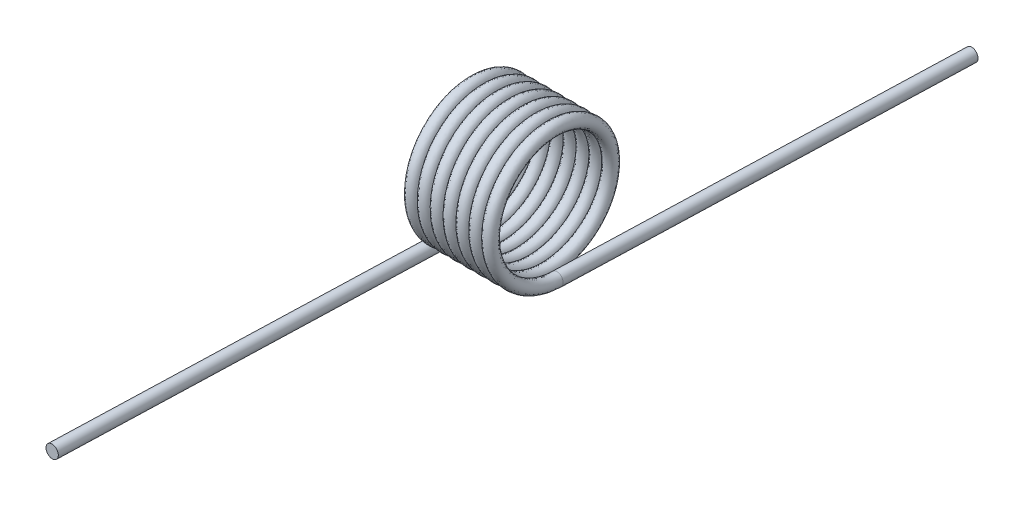
SolidWorks part; units mm, degrees
material "music wire"
ref_plane "Front" through (0, 0, 0) normal (0, 0, 1) x (1, 0, 0)
ref_plane "Top" through (0, 0, 0) normal (0, 1, 0) x (1, 0, 0)
ref_plane "Right" through (0, 0, 0) normal (1, 0, 0) x (0, 0, -1)
sketch "Sketch1" plane through (0, 0, 0) normal (1, 0, 0) x (0, 0, -1)
  line L0 (0, 0) -> (0, -10.7696) construction
  line L1 (0, -10.7696) -> (0, -11.9761) construction
  line L2 (0, -11.9761) -> (0, -13.1826) construction
  circle A0 centre (0, 0) radius 10.7696 construction
  circle A1 centre (0, 0) radius 13.1826 construction
  circle A2 centre (0, 0) radius 11.9761
  circle A3 centre (0, -11.9761) radius 1.2065 construction
  circle A4 centre (0, 0) radius 8.7122 construction
curve "Helix/Spiral1" pitch 2.4384 height 17.0688 radius 11.9761 centre (0, 0, 0) axis (1, 0, 0) start towards (0, 0, -1)
ref_plane "Plane1" through (0, -11.9761, 0) normal (0.0324, 0, -0.9995) x (-0.9995, 0, -0.0324)
sketch "Sketch2" plane through (0, -11.9761, 0) normal (0.0324, 0, -0.9995) x (-0.9995, 0, -0.0324)
  circle A0 centre (0, 0) radius 1.2065
  dimension "D1" = 2.413
sweep "Sweep1" add profiles "Sketch2" path "Helix/Spiral1"
sketch "Sketch3" plane through (0, 0, 0) normal (-0.0324, 0, 0.9995) x (0.9995, 0, 0.0324)
  circle A1 centre (0, -11.9761) radius 1.2065
  circle A2 centre (0, -11.9761) radius 1.2065
  dimension "D1" = 0
extrude "Extrude1" add sketch "Sketch3" along normal blind 76.2
sketch "Sketch4" plane through (0.0179, 0, -0.5525) normal (0.0324, 0, -0.9995) x (-0.9958, -0.0856, -0.0323)
  circle A1 centre (-15.972, -13.3925) radius 1.2065
  circle A2 centre (-15.972, -13.3925) radius 1.2065
  dimension "D1" = 0
extrude "Extrude2" add sketch "Sketch4" along normal blind 76.2
sketch "Sketch5" plane through (0, 0, 0) normal (1, 0, 0) x (0, 0, -1)
  circle A0 centre (0, 0) radius 8.7122 construction
  circle A1 centre (0, 0) radius 8.7122
ref_plane "Plane2" through (0, 0, 0) normal (1, 0, 0) x (0, 0, -1)
ref_axis "Shaft Axis" through (0, 0, 0) along (1, 0, 0)
ref_axis "Wire-End Axis" through (-2.4654, -11.9761, 76.0801) along (0.0324, 0, -0.9995)
equation "\"D4@Helix/Spiral1\"=\"Wire Dia@Sketch1\"+.001"
equation "\"D1@Sketch2\"=\"Wire Dia@Sketch1\""
equation "\"D1@Extrude2\"=\"Leg Length@Extrude1\""
